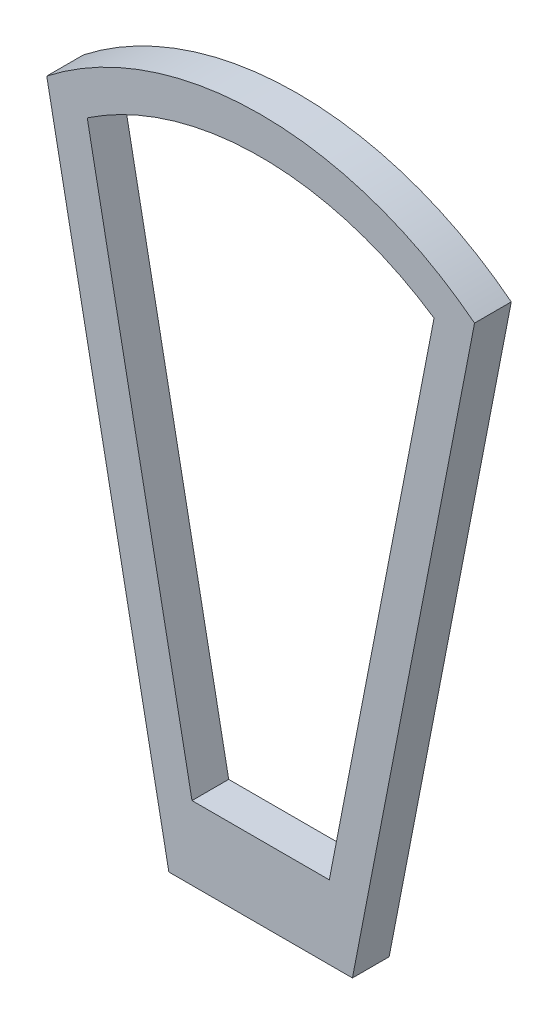
SolidWorks part; units mm, degrees
ref_plane "Front Plane" through (0, 0, 0) normal (0, 0, 1) x (1, 0, 0)
ref_plane "Top Plane" through (0, 0, 0) normal (0, 1, 0) x (1, 0, 0)
ref_plane "Right Plane" through (0, 0, 0) normal (1, 0, 0) x (0, 0, -1)
sketch "Sketch1" plane through (0, 0, 0) normal (0, 0, 1) x (1, 0, 0)
  line L0 (-0.5, -1.7) -> (-1.1652, 1.7224)
  line L1 (-0.5, -1.7) -> (0.5, -1.7)
  line L5 (-0.3351, -1.5) -> (-0.9446, 1.6356)
  line L6 (0.3351, -1.5) -> (0.9446, 1.6356)
  line L7 (0.5, -1.7) -> (1.1652, 1.7224)
  line L8 (-0.3351, -1.5) -> (0.3351, -1.5)
  line L9 (-0.5, -1.7) -> (-0.5, 2.2828) construction
  line L10 (0.5, -1.7) -> (0.5, 2.2828) construction
  arc A0 (-1.1652, 1.7224) -> (1.1652, 1.7224) centre (0, 0.2328) cw
  arc A1 (-0.9446, 1.6356) -> (0.9446, 1.6356) centre (0, 0.2328) cw
  point P0 (0, 0)
  dimension "D2" = 11
  dimension "D3" = 11
  dimension "D1" = 0.2
extrude "Boss-Extrude1" add sketch "Sketch1" along normal blind 0.2
sketch "Sketch3" plane through (0, 0, 0.2) normal (0, 0, 1) x (1, 0, 0)
  line L0 (-0.374, -1.3) -> (0.374, -1.3)
  line L1 (-0.9446, 1.6356) -> (-0.3351, -1.5) construction
  line L2 (0.3351, -1.5) -> (0.9446, 1.6356) construction
  line L3 (-0.5, -1.7) -> (0.5, -1.7) construction
  line L7 (-0.3351, -1.5) -> (0.3351, -1.5)
  line L8 (-0.9446, 1.6356) -> (-0.3351, -1.5)
  line L9 (0.3351, -1.5) -> (0.9446, 1.6356)
  line L10 (-0.3351, -1.5) -> (0.3351, -1.5)
  line L11 (-0.374, -1.3) -> (-0.3351, -1.5)
  line L12 (0.3351, -1.5) -> (0.374, -1.3)
  arc A1 (0.9446, 1.6356) -> (-0.9446, 1.6356) centre (0, 0.2328) ccw
  dimension "D1" = 0.4
  dimension "D2" = 0
extrude "Boss-Extrude2" add sketch "Sketch3" against normal up to surface (0.2 mm away) up to face at (0, 0.1116, 0)
equation "\"D3@Sketch1\"=\"D2@Sketch1\""
